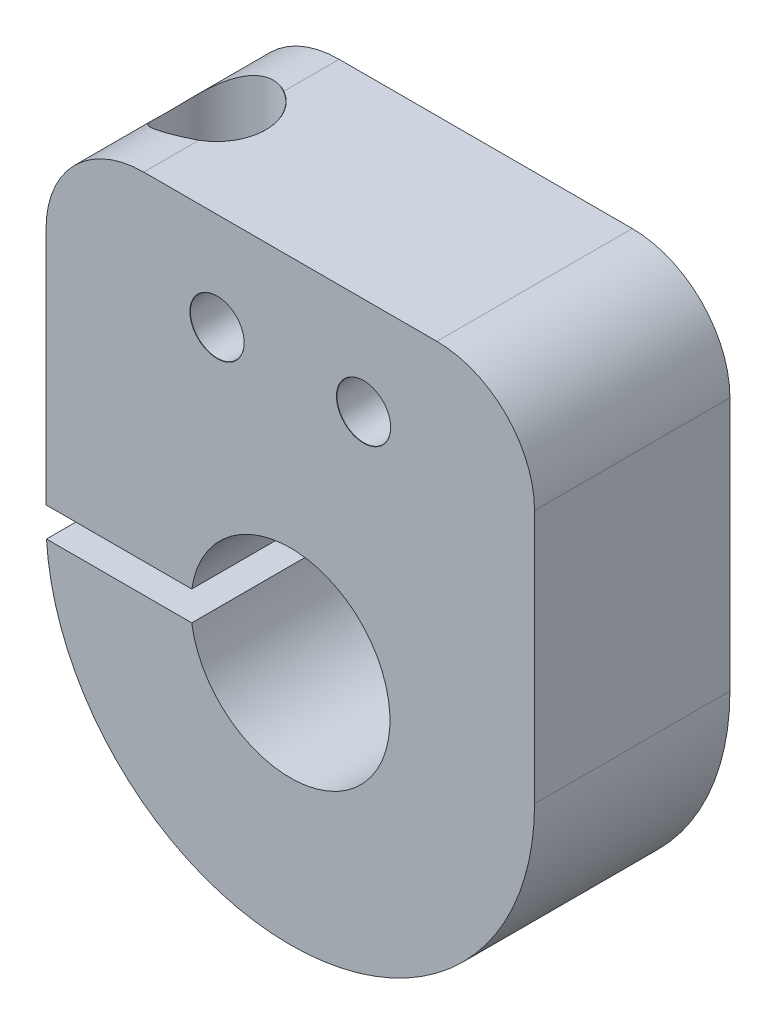
SolidWorks part; units mm, degrees
ref_plane "Front Plane" through (0, 0, 0) normal (0, 0, 1) x (1, 0, 0)
ref_plane "Top Plane" through (0, 0, 0) normal (0, 1, 0) x (1, 0, 0)
ref_plane "Right Plane" through (0, 0, 0) normal (1, 0, 0) x (0, 0, -1)
sketch "Sketch2" plane through (0, 0, 0) normal (0, 0, 1) x (1, 0, 0)
  line L0 (-25, 0) -> (-25, 36)
  line L1 (-25, 36) -> (25, 36)
  line L2 (25, 36) -> (25, 0)
  line L3 (25, 0) -> (-25, 0)
  circle A0 centre (0, 0) radius 25
  circle A1 centre (0, 0) radius 10.2
  dimension "D1" = 20.4
  dimension "D2" = 50
  dimension "D3" = 36
extrude "Boss-Extrude1" add sketch "Sketch2" along normal blind 20 contours A0 L2 L1 L0 | A1 L3 A0 | A1 L3 A0 region at (0, 11.8648, 0) region at (0, 26.8662, 0) region at (0, -11.8648, 0)
sketch "Sketch3" plane through (0, 0, 20) normal (0, 0, 1) x (1, 0, 0)
  line L0 (-25, 0) -> (-25, 36) construction
  line L1 (-25, 1.5) -> (-10.0891, 1.5)
  line L2 (-25, 1.5) -> (-25, -1.5)
  line L3 (-25, -1.5) -> (-10.0891, -1.5)
  line L4 (-10.0891, 1.5) -> (-10.0891, -1.5)
  circle A2 centre (0, 0) radius 10.2 construction
  point P4 (-10.0891, 0)
  dimension "D1" = 3
extrude "Cut-Extrude1" cut sketch "Sketch3" against normal through all
sketch "Sketch11" plane through (0, 36, 0) normal (0, 1, 0) x (1, 0, 0)
  line L1 (-24.955, -20) -> (-10.0891, -20) construction
  line L2 (-25, -20) -> (-25, 0) construction
  point P0 (-17.522, -10)
  point P10 (-17.522, -20)
  point P13 (-25, -10)
hole_wizard "CBORE for M5 SHCS3" positions "Sketch11" profile "Sketch10" counterbore size "M5" standard "ANSI Metric" end condition through all
sketch "Sketch10" plane through (-17.522, 36, 10) normal (1, 0, 0) x (0, 0, 1)
  line L0 (0, 0) -> (0, 61)
  line L1 (0, 61) -> (2.75, 61)
  line L3 (2.75, 61) -> (2.75, 10)
  line L4 (5, 10) -> (2.75, 10)
  line L5 (5, 10) -> (5, 0.025)
  line L6 (5, 0.025) -> (5.025, 0)
  line L7 (5.025, 0) -> (0, 0)
  line L8 (-5, 0.025) -> (-5.025, 0) construction
  line L11 (0, -6.35) -> (0, 107.95) construction
  dimension "Thru Hole Dia." = 5.5
  dimension "Thru Hole Depth" = 61
  dimension "C'Bore Dia." = 10
  dimension "C'Bore Depth" = 10
  dimension "Near C'Sink Dia." = 10.05
  dimension "Near C'Sink Angle" = 90
sketch "Sketch17" plane through (0, 0, 20) normal (0, 0, 1) x (1, 0, 0)
  line L0 (-7.5, 26) -> (7.5, 26) construction
  line L2 (-25, 36) -> (25, 36) construction
  point P0 (-7.5, 26)
  point P2 (7.5, 26)
  point P9 (0, 26)
  dimension "D1" = 15
  dimension "D2" = 10
hole_wizard "M5 Clearance Hole1" positions "Sketch17" profile "Sketch15" hole size "M5" standard "ANSI Metric" end condition through all
sketch "Sketch15" plane through (-7.5, 26, 20) normal (1, 0, 0) x (0, -1, 0)
  line L0 (0, 0) -> (0, 20)
  line L1 (0, 20) -> (2.75, 20)
  line L2 (2.75, 20) -> (2.75, 0.025)
  line L3 (2.75, 0.025) -> (2.775, 0)
  line L5 (2.775, 0) -> (0, 0)
  line L6 (-2.75, 0.025) -> (-2.775, 0) construction
  line L11 (0, -6.35) -> (0, 107.95) construction
  dimension "Thru Hole Dia." = 5.5
  dimension "Thru Hole Depth" = 20
  dimension "Near C'Sink Dia." = 5.55
  dimension "Near C'Sink Angle" = 90
fillet "Fillet1" radius 10 2 edges at (-25, 36, 10) (25, 36, 10)
ref_plane "Plane1" through (0, -11.5, 0) normal (0, 1, 0) x (1, 0, 0)
sketch "Sketch18" plane through (0, -11.5, 0) normal (0, 1, 0) x (1, 0, 0)
  line L0 (-19.8892, -5.9) -> (-15.1549, -5.9)
  line L1 (-15.1549, -5.9) -> (-12.7878, -10)
  line L2 (-12.7878, -10) -> (-15.1549, -14.1)
  line L3 (-15.1549, -14.1) -> (-19.8892, -14.1)
  line L4 (-19.8892, -14.1) -> (-22.2563, -10)
  line L5 (-22.2563, -10) -> (-19.8892, -5.9)
  line L6 (-21.0727, -12.05) -> (-13.9713, -7.95) construction
  line L8 (-25, -20) -> (-25, 0) construction
  line L10 (-24.955, -20) -> (-10.0891, -20) construction
  point P8 (-13.9713, -7.95)
  point P12 (-25, -10)
  point P13 (-17.522, -10)
  point P19 (-17.522, -20)
  dimension "D1" = 120
  dimension "D2" = 120
  dimension "D3" = 8.2
extrude "Cut-Extrude2" cut sketch "Sketch18" against normal through all
